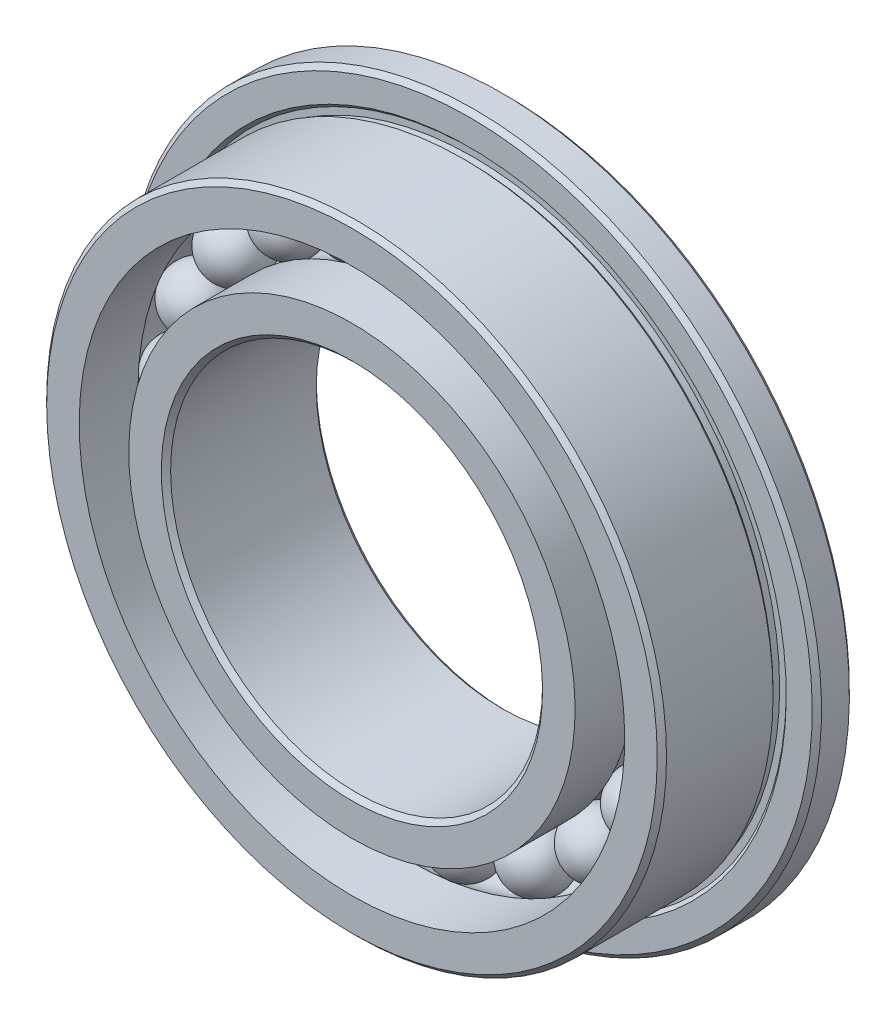
SolidWorks part; units mm, degrees
ref_plane "Front Plane" through (0, 0, 0) normal (0, 0, 1) x (1, 0, 0)
ref_plane "Top Plane" through (0, 0, 0) normal (0, 1, 0) x (1, 0, 0)
ref_plane "Right Plane" through (0, 0, 0) normal (1, 0, 0) x (0, 0, -1)
sketch "Sketch1" plane through (0, 0, 0) normal (1, 0, 0) x (0, 0, -1)
  line L0 (0, 5) -> (0, -5) construction
  line L1 (-1.25, 5) -> (1.25, 5) construction
  line L2 (0, 0) -> (1.25, 0) construction
  line L3 (1.25, 5.6) -> (1.25, -5.6) construction
  line L4 (1.25, -5.6) -> (0.65, -5.6) construction
  line L5 (1.25, 3) -> (0, 3) construction
  line L6 (1.25, 3) -> (1.25, -3) construction
  dimension "OD" = 10
  dimension "Width" = 2.5
  dimension "Flange Thickness" = 0.6
  dimension "ID" = 6
  dimension "Flange OD" = 11.2
sketch "Sketch2" plane through (0, 0, 0) normal (1, 0, 0) x (0, 0, -1)
  line L0 (1.25, 5.6) -> (0.65, 5.6)
  line L1 (0.65, 5.6) -> (0.65, 5.1061)
  line L2 (0.5439, 5) -> (-1.25, 5)
  line L3 (-1.25, 5) -> (-1.25, 4.4)
  line L4 (-1.25, 4.4) -> (-0.3, 4.4)
  line L5 (1.25, 5.6) -> (1.25, -5.6) construction
  line L6 (1.25, 4.4) -> (1.25, 5.6)
  line L7 (1.25, 3) -> (-1.25, 3)
  line L8 (-1.25, 3) -> (-1.25, 3.6)
  line L9 (-1.25, 3.6) -> (-0.3, 3.6)
  line L10 (1.25, 3.6) -> (1.25, 3)
  line L11 (0, 5) -> (0, 3) construction
  line L12 (-0.5, 4) -> (0.5, 4) construction
  line L13 (0.3, 4.4) -> (1.25, 4.4)
  line L14 (0.3, 3.6) -> (1.25, 3.6)
  line L15 (0.65, 5.1061) -> (0.703, 5.053)
  line L16 (0.703, 5.053) -> (0.703, 4.947)
  line L17 (0.703, 4.947) -> (0.597, 4.947)
  line L18 (0.597, 4.947) -> (0.5439, 5)
  line L19 (0.65, 5) -> (0.703, 4.947) construction
  line L20 (0.703, 5.053) -> (0.597, 4.947) construction
  line L21 (0.5439, 5) -> (0.65, 5) construction
  line L22 (0.65, 5) -> (0.65, 5.1061) construction
  circle A0 centre (0, 4) radius 0.5 construction
  arc A1 (-0.3, 4.4) -> (0.3, 4.4) centre (0, 4) cw
  arc A2 (-0.3, 3.6) -> (0.3, 3.6) centre (0, 4) ccw
  dimension "Ball Dia." = 1
  dimension "D2" = 135
  dimension "D3" = 0.15
  dimension "D4" = 0.8
  dimension "Race Thikness" = 0.6
revolve "Revolve1" add sketch "Sketch2" angle 360 about L2
fillet "Fillet1" radius 0.075 3 edges at (0, -5.6, -1.25) (0, -5.6, -0.65) (0, -5, 1.25) profile chamfer
sketch "Sketch3" plane through (0, 0, 0) normal (0, 0, 1) x (1, 0, 0)
  line L0 (-3, 0) -> (3, 0) construction
  line L1 (-5, 0) -> (5, 0) construction
  point P5 (0, 0)
  dimension "ID2" = 6
  dimension "OD2" = 10
fillet "Fillet2" radius 0.075 2 edges at (0, -3, -1.25) (0, -3, 1.25) profile chamfer
sketch "Sketch7" plane through (0, 0, 0) normal (0, 0, 1) x (1, 0, 0)
  line L0 (0, 4.5) -> (0, 3.5)
  line L1 (0, 5.6) -> (0, -5.6) construction
  line L2 (-0.5669, 4.5) -> (0, 0) construction
  line L3 (0, 0) -> (0.5669, 4.5) construction
  line L4 (0.5669, 4.5) -> (-0.5669, 4.5) construction
  circle A0 centre (0, 4) radius 0.5 construction
  circle A1 centre (0, 0) radius 4.5 construction
  circle A2 centre (0, 0) radius 3.5 construction
  arc A4 (0, 4.5) -> (0, 3.5) centre (0, 4) ccw
  dimension "D1" = 14.362
revolve "Revolve3" add sketch "Sketch7" angle 360 about L0
pattern_circular "CirPattern3" count 21 over 360 about axis through (0, 0, 0) along (0, 0, -1) of bodies 107
sketch "Sketch8" plane through (0, 0, 0) normal (1, 0, 0) x (0, 0, -1)
  line L0 (-1.25, 5) -> (1.25, 5) construction
  line L1 (1.25, 5) -> (1.25, 5.6) construction
  line L2 (-1.25, -5) -> (1.25, -5) construction
  line L3 (1.25, 5.6) -> (1.25, -5.6) construction
  dimension "D1" = 10
equation "\"Ball Dia.@Sketch2\" = ( \"OD@Sketch1\" - \"ID@Sketch1\" ) * .25"
equation "\"D3@Sketch2\"=\"Flange Thickness@Sketch1\"/4"
equation "\"D1@Fillet1\" = \"Race Thikness@Sketch2\" / 8"
equation "\"ID2@Sketch3\" = \"ID@Sketch1\""
equation "\"OD2@Sketch3\" = \"OD@Sketch1\""
equation "\"D1@Fillet2\" = \"Race Thikness@Sketch2\" / 8"
equation "\"D1@CirPattern3\"=360/\"D1@Sketch7\"-4"
equation "\"D4@Sketch2\" = ( \"OD@Sketch1\" - \"ID@Sketch1\" ) * .2"
